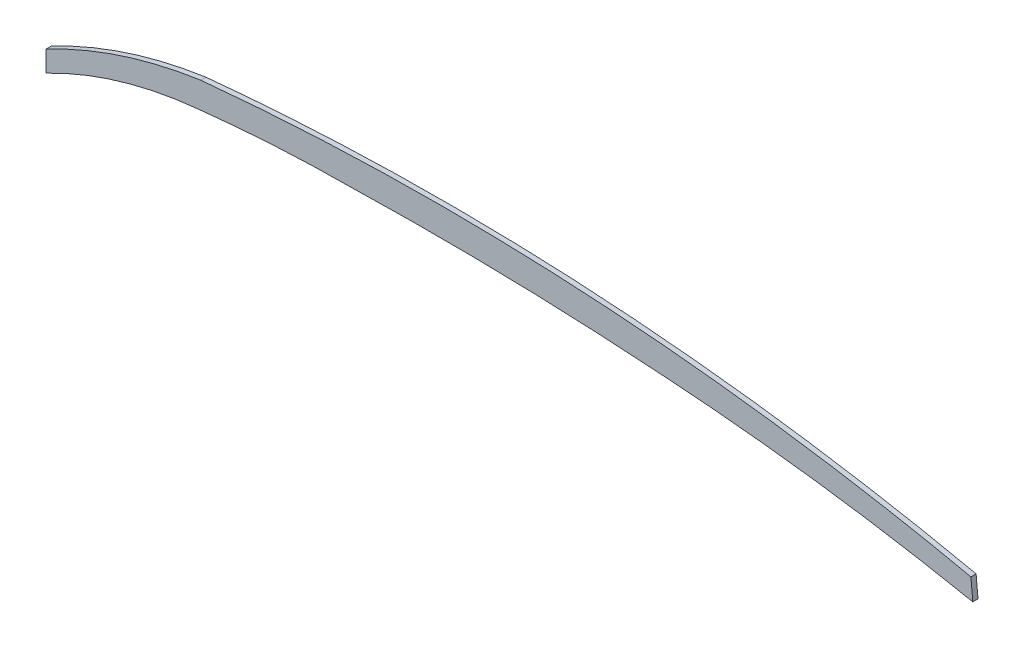
SolidWorks part; units mm, degrees
material "Balsa"
ref_plane "Front Plane" through (0, 0, 0) normal (0, 0, 1) x (1, 0, 0)
ref_plane "Top Plane" through (0, 0, 0) normal (0, 1, 0) x (1, 0, 0)
ref_plane "Right Plane" through (0, 0, 0) normal (1, 0, 0) x (0, 0, -1)
sketch "Sketch1" plane through (0, 0, 0) normal (0, 0, 1) x (1, 0, 0)
  line L0 (0, 85.9425) -> (0, 98.6503)
  line L1 (566.0852, 89.3165) -> (564.9321, 101.9675)
  arc A6 (0, 85.9425) -> (92.3925, 113.3646) centre (117.1549, -139.4255) cw
  arc A7 (92.3925, 113.3646) -> (185.8959, 118.7316) centre (190.0181, -770.2588) cw
  arc A8 (0, 98.6503) -> (94.4926, 129.4761) centre (136.5172, -159.585) cw
  arc A9 (185.8959, 118.7316) -> (373.1011, 114.6803) centre (236.8429, -1854.3326) cw
  arc A10 (373.1011, 114.6803) -> (566.0852, 89.3165) centre (283.2319, -1315.9598) cw
  spline S6 degree 3 poles (2049.108, -1178.3828) (1578.8722, -392.9324) (1045.2789, 40.9031) (438.4396, 123.9347) (428.6248, 125.1803) (408.999, 127.4768) (399.1847, 128.5284) (369.7378, 131.3944) (350.1011, 132.9205) (291.1746, 136.3531) (251.8686, 137.116) (-364.4559, 125.1938) (-946.1148, -213.9223) (-1533.6104, -963.6327) knots -3.560325 -3.560325 -3.560325 -3.560325 0.25 0.25 0.3125 0.3125 0.375 0.375 0.5 0.5 0.75 0.75 4.417882 4.417882 4.417882 4.417882 only from (564.9321, 101.9675) to (94.4926, 129.4761)
  spline S7 degree 3 poles (564.9321, 101.9675) (526.3055, 110.3591) (487.4057, 117.2349) (438.4396, 123.9347) (428.6248, 125.1803) (408.999, 127.4768) (399.1847, 128.5284) (369.7378, 131.3944) (350.1011, 132.9205) (291.1746, 136.3531) (251.8686, 137.116) (173.2133, 135.5945) (133.864, 133.3102) (94.4926, 129.4761) knots 0 0 0 0 0.25 0.25 0.3125 0.3125 0.375 0.375 0.5 0.5 0.75 0.75 1 1 1 1
  dimension "D4" = 92.3925
  dimension "D2" = 254
  dimension "D8" = 187.2051
  dimension "D9" = 28.7378
  dimension "D1" = 292.1
  dimension "D3" = 889
  dimension "D10" = 1973.7219
  dimension "D11" = 1433.46
  dimension "D5" = 27.4221
  dimension "D6" = 93.5034
  dimension "D7" = 32.7892
extrude "Boss-Extrude1" add sketch "Sketch1" against normal mid plane 3.175 contours L1 S7 A8 L0 A6 A7 A9 A10 region at (279.3924, 119.3666, 0)
equation "\"slotwidth\"=0.167708"
